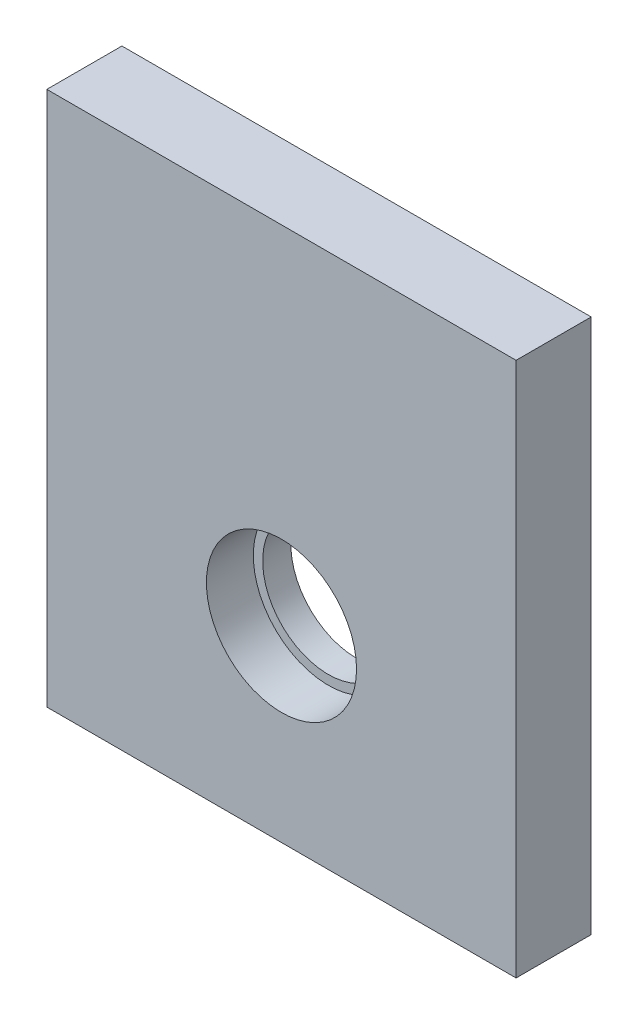
SolidWorks part; units mm, degrees
ref_plane "Front" through (0, 0, 0) normal (0, 0, 1) x (1, 0, 0)
ref_plane "Top" through (0, 0, 0) normal (0, 1, 0) x (1, 0, 0)
ref_plane "Right" through (0, 0, 0) normal (1, 0, 0) x (0, 0, -1)
sketch "Esquisse1" plane through (0, 0, 0) normal (0, 0, 1) x (1, 0, 0)
  line L0 (25, 0) -> (25, 20) construction
  line L1 (0, 0) -> (50, 0)
  line L2 (0, 0) -> (0, 57)
  line L3 (0, 57) -> (50, 57)
  line L4 (50, 0) -> (50, 57)
  circle A0 centre (25, 20) radius 7
  dimension "D1" = 20
  dimension "D2" = 14
  dimension "D3" = 50
  dimension "D4" = 57
extrude "Boss.-Extru.1" add sketch "Esquisse1" along normal blind 8
sketch "Esquisse2" plane through (0, 0, 8) normal (0, 0, 1) x (1, 0, 0)
  circle A0 centre (25, 20) radius 8
  dimension "D1" = 16
extrude "Enlèv. mat.-Extru.1" cut sketch "Esquisse2" against normal blind 5
